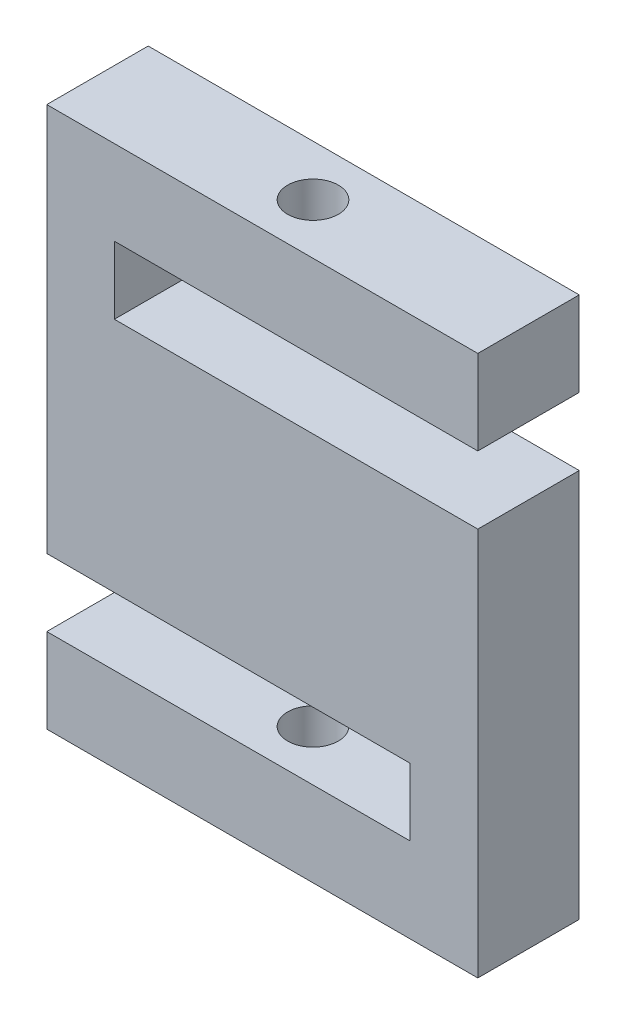
SolidWorks part; units mm, degrees
ref_plane "Płaszczyzna przednia" through (0, 0, 0) normal (0, 0, 1) x (1, 0, 0)
ref_plane "Płaszczyzna górna" through (0, 0, 0) normal (0, 1, 0) x (1, 0, 0)
ref_plane "Płaszczyzna prawa" through (0, 0, 0) normal (1, 0, 0) x (0, 0, -1)
sketch "Szkic1" plane through (0, 0, 0) normal (0, 0, 1) x (1, 0, 0)
  line L0 (-25.5, 22) -> (25.5, 22) construction
  line L1 (25.5, -32) -> (-25.5, -32) construction
  line L2 (25.5, -32) -> (25.5, 32) construction
  line L3 (25.5, 32) -> (-25.5, 32) construction
  line L4 (-25.5, -32) -> (-25.5, 32) construction
  line L5 (25.5, -32) -> (-25.5, 32) construction
  line L6 (25.5, 32) -> (-25.5, -32) construction
  line L7 (25.5, -22) -> (-25.5, -22) construction
  line L8 (-17.5, 32) -> (-17.5, -32) construction
  line L9 (17.5, 32) -> (17.5, -32) construction
  line L10 (-17.5, -14) -> (17.5, -14) construction
  line L11 (17.5, 14) -> (-17.5, 14) construction
  line L12 (-25.5, -22) -> (-25.5, -32)
  line L13 (-25.5, -32) -> (25.5, -32)
  line L14 (25.5, -32) -> (25.5, 14)
  line L15 (25.5, 14) -> (-17.5, 14)
  line L16 (-17.5, 14) -> (-17.5, 22)
  line L17 (-17.5, 22) -> (25.5, 22)
  line L18 (25.5, 22) -> (25.5, 32)
  line L19 (25.5, 32) -> (-25.5, 32)
  line L20 (-25.5, 32) -> (-25.5, -14)
  line L21 (-25.5, -14) -> (17.5, -14)
  line L22 (17.5, -14) -> (17.5, -21.9608)
  line L23 (17.5, -21.9608) -> (-25.5, -22)
  point P0 (0, 0)
  dimension "D1" = 64
  dimension "D2" = 51
  dimension "D3" = 10
  dimension "D4" = 10
  dimension "D5" = 8
  dimension "D6" = 8
  dimension "D7" = 8
  dimension "D8" = 8
extrude "Dodanie-wyciągnięcie1" add sketch "Szkic1" along normal blind 12
sketch "Szkic2" plane through (0, 0, 0) normal (0, 1, 0) x (1, 0, 0)
  line L0 (0, 0) -> (0, -12) construction
  line L1 (25.5, -12) -> (-25.5, -12) construction
  circle A0 centre (0, -6) radius 3
  point P7 (0, -6)
  dimension "D1" = 6
extrude "Wytnij-wyciągnięcie1" cut sketch "Szkic2" against normal blind 12 from surface starting at face at (0, 32, 6)
extrude "Wytnij-wyciągnięcie2" cut sketch "Szkic2<2>" along normal blind 12 from surface starting at face at (0, -32, 6)
sketch "Szkic2<2>" plane through (0, 0, 0) normal (0, 1, 0) x (1, 0, 0) same geometry as "Szkic2"
